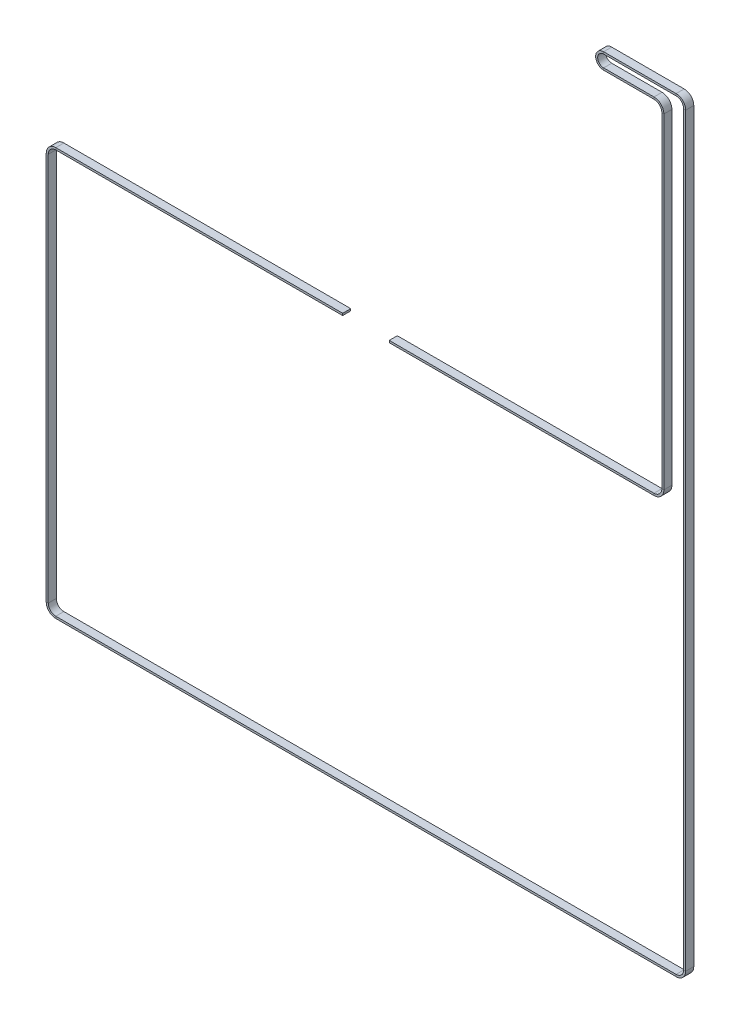
SolidWorks part; units mm, degrees
ref_plane "Front" through (0, 0, 0) normal (0, 0, 1) x (1, 0, 0)
ref_plane "Top" through (0, 0, 0) normal (0, 1, 0) x (1, 0, 0)
ref_plane "Right" through (0, 0, 0) normal (1, 0, 0) x (0, 0, -1)
sketch "Sketch1" plane through (0, 0, 2.2) normal (0, 0, 1) x (1, 0, 0)
  line L0 (377.3122, -142.2854) -> (431.3122, -142.2854)
  line L1 (377.3122, -152.6854) -> (414.8122, -152.6854)
  line L2 (421.4122, -159.2854) -> (421.4122, -401.6854)
  line L3 (437.6872, -148.6604) -> (437.6872, -703.9854)
  line L4 (-37.0628, -703.9854) -> (-37.0628, -414.5104)
  line L5 (431.3122, -710.3604) -> (-30.6878, -710.3604)
  line L6 (-30.6878, -408.1354) -> (182.9622, -408.1354)
  line L7 (217.6622, -406.6854) -> (217.6622, -411.6854) construction
  line L9 (414.8122, -408.2854) -> (217.6622, -408.2854)
  line L10 (182.9622, -411.6854) -> (182.9622, -406.6854) construction
  circle A0 centre (414.8122, -159.2854) radius 6.6 construction
  circle A1 centre (431.3122, -148.6604) radius 6.375 construction
  circle A2 centre (377.3122, -147.4854) radius 5.2 construction
  arc A3 (431.3122, -142.2854) -> (437.6872, -148.6604) centre (431.3122, -148.6604) cw
  arc A4 (377.3122, -152.6854) -> (377.3122, -142.2854) centre (377.3122, -147.4854) cw
  arc A5 (414.8122, -152.6854) -> (421.4122, -159.2854) centre (414.8122, -159.2854) cw
  circle A6 centre (-30.6878, -703.9854) radius 6.375 construction
  arc A7 (-30.6878, -710.3604) -> (-37.0628, -703.9854) centre (-30.6878, -703.9854) cw
  circle A8 centre (431.3122, -148.6604) radius 9 construction
  circle A9 centre (414.8122, -159.2854) radius 9 construction
  circle A10 centre (-30.6878, -414.5104) radius 6.375 construction
  circle A11 centre (431.3122, -703.9854) radius 6.375 construction
  arc A12 (437.6872, -703.9854) -> (431.3122, -710.3604) centre (431.3122, -703.9854) cw
  arc A13 (-37.0628, -414.5104) -> (-30.6878, -408.1354) centre (-30.6878, -414.5104) cw
  circle A14 centre (414.8122, -401.6854) radius 6.6 construction
  arc A15 (421.4122, -401.6854) -> (414.8122, -408.2854) centre (414.8122, -401.6854) cw
  circle A16 centre (414.8122, -401.6854) radius 5.9875 construction
  circle A17 centre (-30.6878, -414.5104) radius 5.9875 construction
  dimension "D1" = 12.75
ref_plane "Plane1" through (182.9622, -408.1354, 2.2) normal (1, 0, 0) x (0, 0, -1)
sketch "Sketch4" plane through (182.9622, -408.1354, 2.2) normal (1, 0, 0) x (0, 0, -1)
  line L0 (0, 259.475) -> (0, -295.85) construction
  line L1 (3, -0.75) -> (-3, -0.75)
  line L2 (3, -0.75) -> (3, 0.75)
  line L3 (3, 0.75) -> (-3, 0.75)
  line L4 (-3, -0.75) -> (-3, 0.75)
  line L5 (3, -0.75) -> (-3, 0.75) construction
  line L6 (3, 0.75) -> (-3, -0.75) construction
  line L7 (0, 0) -> (0, -12.75) construction
  point P0 (0, 0)
  dimension "D1" = 1.5
  dimension "D2" = 6
sweep "Sweep1" add profiles "Sketch4" path "Sketch1"
